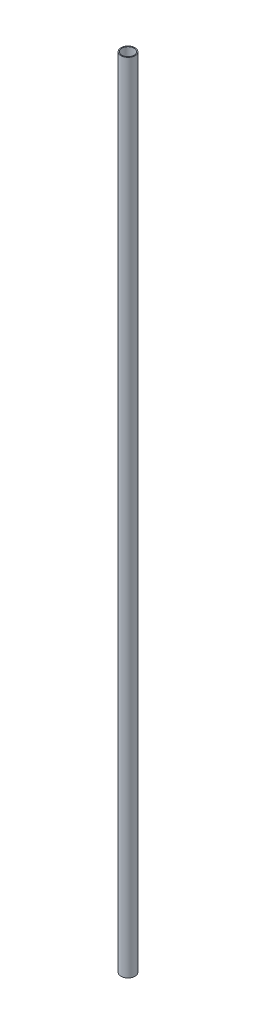
SolidWorks part; units mm, degrees
ref_plane "前视基准面" through (0, 0, 0) normal (0, 0, 1) x (1, 0, 0)
ref_plane "上视基准面" through (0, 0, 0) normal (0, 1, 0) x (1, 0, 0)
ref_plane "右视基准面" through (0, 0, 0) normal (1, 0, 0) x (0, 0, -1)
other "Configuration Table"
sketch "草图1" plane through (0, 0, 0) normal (0, 1, 0) x (1, 0, 0)
  circle A0 centre (0, 0) radius 8
  circle A1 centre (0, 0) radius 7
  dimension "D1" = 1
extrude "凸台-拉伸1" add sketch "草图1" along normal blind 913 contours A0 A1 region at (-7.7737, 0, 0)
ref_axis "基准轴1" through (0, 913, 0) along (0, -1, 0)
